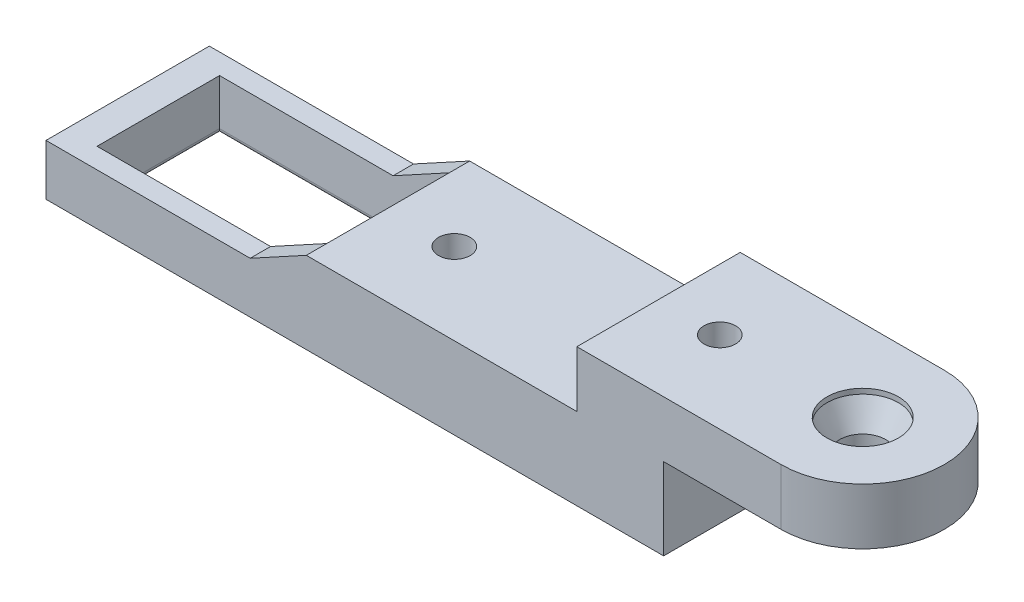
SolidWorks part; units mm, degrees
ref_plane "Front Plane" through (0, 0, 0) normal (0, 0, 1) x (1, 0, 0)
ref_plane "Top Plane" through (0, 0, 0) normal (0, 1, 0) x (1, 0, 0)
ref_plane "Right Plane" through (0, 0, 0) normal (1, 0, 0) x (0, 0, -1)
sketch "Sketch1" plane through (0, 0, 0) normal (0, 1, 0) x (1, 0, 0)
  line L0 (-14.25, 8) -> (-14.25, -8)
  line L1 (-11.25, -6) -> (11.25, -6)
  line L2 (-11.25, -6) -> (-11.25, 6)
  line L3 (-11.25, 6) -> (11.25, 6)
  line L4 (11.25, -6) -> (11.25, 6)
  line L5 (-11.25, -6) -> (11.25, 6) construction
  line L6 (-11.25, 6) -> (11.25, -6) construction
  line L7 (-14.25, -8) -> (20, -8)
  line L8 (-20, -8) -> (-20, 8) construction
  line L9 (-14.25, 8) -> (20, 8)
  line L10 (20, -8) -> (20, 8)
  line L11 (-20, -8) -> (20, 8) construction
  line L12 (-20, 8) -> (20, -8) construction
  line L13 (-20, 8) -> (-14.25, 8) construction
  line L14 (-20, -8) -> (-14.25, -8) construction
  point P0 (0, 0)
  point P6 (0, 0)
  dimension "D1" = 22.5
  dimension "D2" = 12
  dimension "D3" = 40
  dimension "D4" = 16
  dimension "D5" = 3
extrude "Boss-Extrude2" add sketch "Sketch1" along normal blind 5
sketch "Sketch4" plane through (20, 0, 0) normal (1, 0, 0) x (0, 0, -1)
  line L1 (-8, 5) -> (8, 5)
  line L2 (-8, 5) -> (-8, 0)
  line L3 (-8, 0) -> (8, 0)
  line L4 (8, 5) -> (8, 0)
extrude "Boss-Extrude3" add sketch "Sketch4" along normal blind 2
sketch "Sketch3" plane through (0, 5, 0) normal (0, 1, 0) x (1, 0, 0)
  line L0 (-11.25, 6) -> (5.75, 6) construction
  line L1 (11.25, 6) -> (-11.25, 6) construction
  line L2 (5.75, 6) -> (5.75, 0) construction
  line L3 (-11.25, -6) -> (11.25, -6) construction
  line L4 (5.75, 6) -> (7.25, 6) construction
  line L5 (7.25, 6) -> (7.25, -6) construction
  line L6 (5.75, 6) -> (11.25, 6)
  line L7 (5.75, 0) -> (19.1059, 0) construction
  line L8 (22, 8) -> (5.75, 8)
  line L9 (22, 8) -> (-14.25, 8) construction
  line L10 (5.75, 8) -> (5.75, 6)
  line L11 (-14.25, -8) -> (22, -8) construction
  line L12 (5.75, -8) -> (22, -8)
  line L13 (22, -8) -> (22, 8)
  line L14 (11.25, 6) -> (11.25, -6)
  line L15 (11.25, -6) -> (5.75, -6)
  line L16 (5.75, 0) -> (5.75, -6) construction
  line L17 (5.75, -6) -> (5.75, -8)
  line L18 (5.75, 0) -> (5.75, -6) construction
  line L19 (5.75, 6) -> (5.75, 0) construction
  dimension "D1" = 1.5
  dimension "D2" = 17
extrude "Boss-Extrude4" add sketch "Sketch3" along normal blind 3
sketch "Sketch6" plane through (0, 8, 0) normal (0, 1, 0) x (1, 0, 0)
  line L0 (-5.25, 6) -> (-5.25, -6) construction
  line L5 (-11.25, -6) -> (5.75, -6) construction
  line L6 (-11.25, 6) -> (-11.25, -6) construction
  line L7 (-11.25, 6) -> (5.75, 6) construction
  line L8 (-11.25, 0) -> (22, 0) construction
  line L9 (22, -8) -> (22, 8) construction
  line L10 (17.75, 8) -> (17.75, -8) construction
  line L11 (22, 8) -> (5.75, 8) construction
  line L12 (5.75, -8) -> (22, -8) construction
  circle A0 centre (17.75, 0) radius 1.55
  dimension "D3" = 3.1
  dimension "D1" = 6
  dimension "D2" = 23
extrude "Cut-Extrude1" cut sketch "Sketch6" against normal blind 3.5
fillet "Fillet1" radius 0.5 4 edges at (11.25, 0, 0) (0, 0, -6) (-11.25, 0, 0) (0, 0, 6)
sketch "Sketch8" plane through (0, 8, 0) normal (0, 1, 0) x (1, 0, 0)
  line L0 (22, 8) -> (47.75, 8)
  line L1 (22, 8) -> (22, -8)
  line L2 (22, -8) -> (47.75, -8)
  line L3 (47.75, -8) -> (47.75, 8)
  line L4 (43.75, 8) -> (43.75, -8) construction
  line L5 (47.75, 0) -> (43.75, 0) construction
  dimension "D1" = 30
  dimension "D2" = 4
extrude "Boss-Extrude5" add sketch "Sketch8" against normal up to surface (8 mm away) up to face at (0, 0, 0)
sketch "Sketch9" plane through (0, 8, 0) normal (0, 1, 0) x (1, 0, 0)
  line L0 (5.75, -8) -> (47.75, -8) construction
  line L1 (47.75, 8) -> (37.75, 8)
  line L2 (47.75, 8) -> (47.75, -8)
  line L3 (47.75, -8) -> (37.75, -8)
  line L4 (37.75, 8) -> (37.75, -8)
  dimension "D1" = 10
extrude "Boss-Extrude6" add sketch "Sketch9" along normal blind 5.5
sketch "Sketch10" plane through (0, 13.5, 0) normal (0, 1, 0) x (1, 0, 0)
  line L0 (43.75, 8) -> (43.75, -8) construction
  circle A0 centre (43.75, 0) radius 1.55
  dimension "D1" = 3.1
extrude "Cut-Extrude2" cut sketch "Sketch10" against normal blind 3.5
sketch "Sketch11" plane through (47.75, 0, 0) normal (1, 0, 0) x (0, 0, -1)
  line L1 (-8, 13.5) -> (8, 13.5)
  line L2 (-8, 13.5) -> (-8, 8)
  line L3 (-8, 8) -> (8, 8)
  line L4 (8, 13.5) -> (8, 8)
  line L5 (8, 0) -> (8, 13.5) construction
  line L6 (8, 8) -> (-8, 8) construction
extrude "Boss-Extrude7" add sketch "Sketch11" along normal blind 20
sketch "Sketch12" plane through (0, 13.5, 0) normal (0, 1, 0) x (1, 0, 0)
  line L0 (47.75, 0) -> (67.75, 0) construction
  line L1 (67.75, 8) -> (67.75, -8) construction
  line L2 (47.75, 0) -> (47.75, 8) construction
  line L3 (47.75, 8) -> (67.75, 8) construction
  line L4 (57.75, 8) -> (57.75, -8) construction
  line L5 (37.75, -8) -> (67.75, -8) construction
  line L6 (57.75, 8) -> (67.75, 8)
  line L7 (67.75, 8) -> (67.75, -8)
  line L8 (67.75, -8) -> (57.75, -8)
  circle A0 centre (57.75, 0) radius 2.25
  arc A1 (57.75, -8) -> (57.75, 8) centre (57.75, 0) ccw
  arc A2 (49.75, 0) -> (57.75, -8) centre (57.75, 0) ccw construction
  arc A3 (57.75, 8) -> (49.75, 0) centre (57.75, 0) ccw construction
  dimension "D1" = 4.5
extrude "Cut-Extrude3" cut sketch "Sketch12" against normal through all both and the other way through all
sketch "Sketch13" plane through (0, 13.5, 0) normal (0, 1, 0) x (1, 0, 0)
  circle A0 centre (57.75, 0) radius 3.5
  dimension "D1" = 7
extrude "Cut-Extrude4" cut sketch "Sketch13" against normal blind 3
sketch "Sketch14" plane through (0, 0, -8) normal (0, 0, -1) x (-1, 0, 0)
  line L0 (-47.75, 0) -> (14.25, 0) construction
  line L1 (-47.75, 8) -> (-46.25, 8)
  line L2 (-47.75, 8) -> (-47.75, 0)
  line L3 (-47.75, 0) -> (-46.25, 0)
  line L4 (-46.25, 8) -> (-46.25, 0)
  dimension "D1" = 1.5
extrude "Cut-Extrude5" cut sketch "Sketch14" against normal through all
chamfer "Chamfer1" distance 2.5 distance2 1.25 1 edges at (57.75, 10.5, 3.5) first distance on face at (57.75, 10.5, 3.5)
chamfer "Chamfer2" distance 3 distance2 5.5 2 edges at (5.75, 8, 7) (5.75, 8, -7) first distance on face at (5.75, 6.5, 7) first distance on face at (5.75, 6.5, -7)
